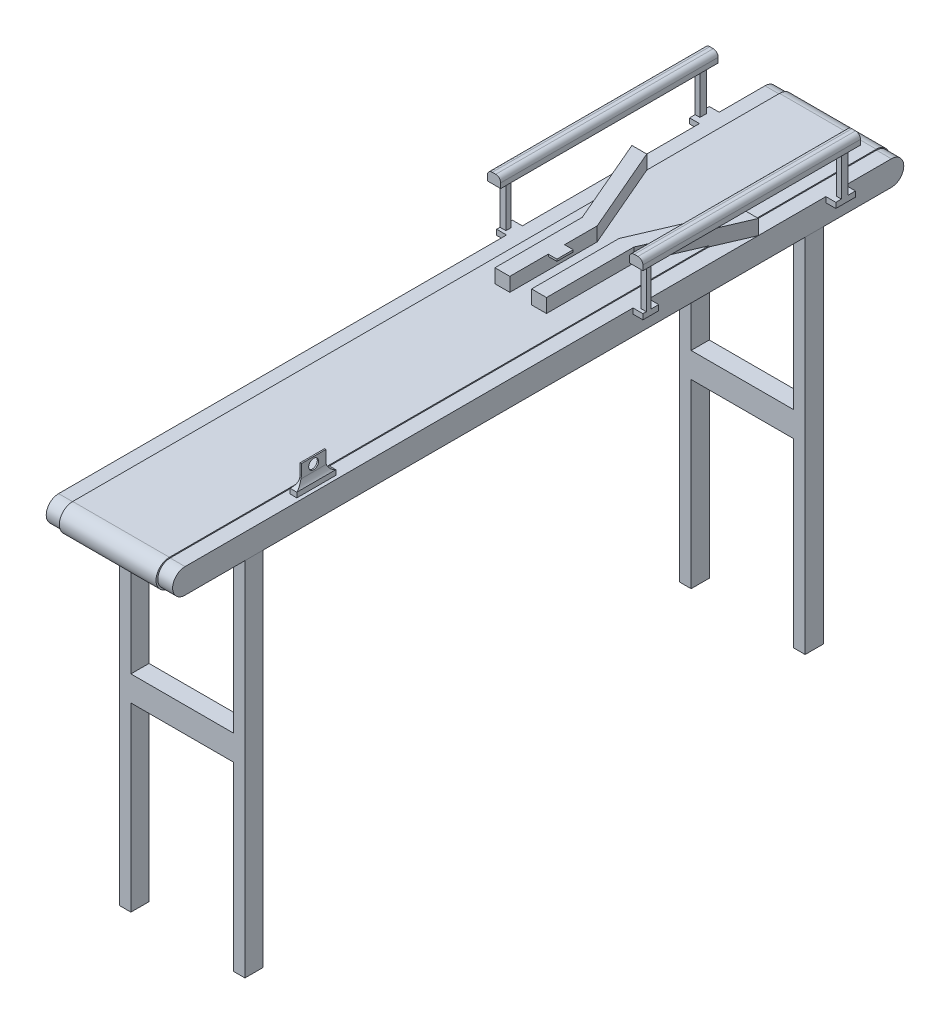
SolidWorks part; units mm, degrees
ref_plane "Alzado" through (0, 0, 0) normal (0, 0, 1) x (1, 0, 0)
ref_plane "Planta" through (0, 0, 0) normal (0, 1, 0) x (1, 0, 0)
ref_plane "Vista lateral" through (0, 0, 0) normal (1, 0, 0) x (0, 0, -1)
sketch "Croquis1" plane through (0, 0, 0) normal (0, 1, 0) x (1, 0, 0)
  line L1 (0, 0) -> (-255, 0)
  line L2 (0, 0) -> (0, 1475)
  line L3 (0, 1475) -> (-255, 1475)
  line L4 (-255, 0) -> (-255, 1475)
  dimension "D1" = 255
  dimension "D2" = 1475
extrude "Saliente-Extruir1" add sketch "Croquis1" along normal blind 50
sketch "Croquis2" plane through (-255, 0, 0) normal (-1, 0, 0) x (0, 0, 1)
  line L0 (6.4584, -12.3806) -> (-25, 0)
  line L4 (-1481.2344, 62.3806) -> (-1449.776, 50)
  line L8 (-1449.776, 0) -> (-1480.215, -12.0359)
  line L9 (-1480.215, -12.0359) -> (-1481.2344, 62.3806)
  line L11 (-25, 50) -> (5.439, 62.0359)
  line L12 (5.439, 62.0359) -> (6.4584, -12.3806)
  line L13 (-1475, 0) -> (0, 0) construction
  arc A4 (-25, 50) -> (-25, 0) centre (-25, 25) cw
  arc A5 (-1449.776, 0) -> (-1449.776, 50) centre (-1449.776, 25) cw
extrude "Cortar-Extruir1" cut sketch "Croquis2" against normal through all
sketch "Croquis5" plane through (-255, 0, 0) normal (-1, 0, 0) x (0, 0, 1)
  line L0 (-1449.776, 0) -> (-25, 0) construction
  line L2 (-1449.276, 52) -> (-23.5, 52)
  line L3 (-23.5, -2) -> (-1449.276, -2)
  arc A1 (-23.5, -2) -> (-23.5, 52) centre (-23.5, 25) ccw
  arc A2 (-25, 0) -> (-25, 50) centre (-25, 25) ccw construction
  arc A3 (-1449.276, 52) -> (-1449.276, -2) centre (-1449.276, 25) ccw
  arc A5 (-1449.776, 50) -> (-1449.776, 0) centre (-1449.776, 25) ccw construction
  point P18 (-1474.776, 25)
  point P19 (-1476.276, 25)
  dimension "D1" = 27
  dimension "D3" = 1.5
  dimension "D5" = 27
  dimension "D2" = 25
  dimension "D4" = 25
  dimension "D6" = 1.5
extrude "Saliente-Extruir2" add sketch "Croquis5" against normal blind 195 from offset 30 offset against normal yes
sketch "Croquis6" plane through (0, 0, 0) normal (0, -1, 0) x (1, 0, 0)
  line L0 (-255, -1449.776) -> (-255, -25) construction
  line L1 (-255, -147.7299) -> (-231.9101, -147.7299)
  line L2 (-255, -147.7299) -> (-255, -184.3095)
  line L3 (-255, -184.3095) -> (-231.9101, -184.3095)
  line L4 (-231.9101, -147.7299) -> (-231.9101, -184.3095)
  line L5 (-25, -147.7299) -> (-25, -184.3095)
  line L6 (-25, -147.7299) -> (-1.9101, -147.7299)
  line L7 (-1.9101, -147.7299) -> (-1.9101, -184.3095)
  line L8 (-25, -184.3095) -> (-1.9101, -184.3095)
  line L9 (-25, -1277.7299) -> (-25, -1314.3095)
  line L10 (-25, -1277.7299) -> (-1.9101, -1277.7299)
  line L11 (-1.9101, -1277.7299) -> (-1.9101, -1314.3095)
  line L12 (-25, -1314.3095) -> (-1.9101, -1314.3095)
  line L13 (-255, -1277.7299) -> (-255, -1314.3095)
  line L14 (-255, -1277.7299) -> (-231.9101, -1277.7299)
  line L15 (-231.9101, -1277.7299) -> (-231.9101, -1314.3095)
  line L16 (-255, -1314.3095) -> (-231.9101, -1314.3095)
  dimension "D1" = 2
  dimension "D2" = 2
extrude "Saliente-Extruir3" add sketch "Croquis6" along normal blind 731
sketch "Croquis7" plane through (-1.9101, 0, 0) normal (1, 0, 0) x (0, 0, -1)
  line L0 (147.7299, -731) -> (147.7299, 0) construction
  line L1 (147.7299, -314.7831) -> (184.3095, -314.7831)
  line L2 (147.7299, -314.7831) -> (147.7299, -365.5)
  line L3 (147.7299, -365.5) -> (184.3095, -365.5)
  line L4 (184.3095, -314.7831) -> (184.3095, -365.5)
  line L5 (184.3095, -731) -> (184.3095, 0) construction
  line L6 (1277.7299, -731) -> (1277.7299, 0) construction
  line L7 (1277.7299, -365.5) -> (1314.3095, -365.5)
  line L8 (1277.7299, -365.5) -> (1277.7299, -314.7831)
  line L9 (1277.7299, -314.7831) -> (1314.3095, -314.7831)
  line L10 (1314.3095, -365.5) -> (1314.3095, -314.7831)
  line L11 (1314.3095, -731) -> (1314.3095, 0) construction
extrude "Saliente-Extruir4" add sketch "Croquis7" against normal through all
sketch "Croquis9" plane through (-255, 0, 0) normal (-1, 0, 0) x (0, 0, 1)
  line L0 (-1449.776, 50) -> (-25, 50) construction
  line L1 (-1357.4324, 50) -> (-1317.6624, 50)
  line L2 (-1357.4324, 50) -> (-1357.4324, 39.2137)
  line L3 (-1357.4324, 39.2137) -> (-1317.6624, 39.2137)
  line L4 (-1317.6624, 50) -> (-1317.6624, 39.2137)
  line L5 (-1449.776, 50) -> (-25, 50) construction
  line L6 (-960.3915, 50) -> (-928.5918, 50)
  line L7 (-960.3915, 50) -> (-960.3915, 39.2137)
  line L8 (-960.3915, 39.2137) -> (-928.5918, 39.2137)
  line L9 (-928.5918, 50) -> (-928.5918, 39.2137)
extrude "Saliente-Extruir5" add sketch "Croquis9" against normal blind 275 and the other way blind 20
sketch "Croquis10" plane through (0, 50, 0) normal (0, 1, 0) x (1, 0, 0)
  line L0 (-275, 1317.6624) -> (-275, 1357.4324) construction
  line L1 (-275, 1342.1015) -> (-265.3595, 1342.1015)
  line L2 (-275, 1342.1015) -> (-275, 1328.9734)
  line L3 (-275, 1328.9734) -> (-265.3595, 1328.9734)
  line L4 (-265.3595, 1342.1015) -> (-265.3595, 1328.9734)
  line L5 (20, 1317.6624) -> (20, 1357.4324) construction
  line L6 (20, 1342.1015) -> (9.6893, 1342.1015)
  line L7 (20, 1342.1015) -> (20, 1328.9734)
  line L8 (20, 1328.9734) -> (9.6893, 1328.9734)
  line L9 (9.6893, 1342.1015) -> (9.6893, 1328.9734)
  line L10 (-275, 928.5918) -> (-275, 960.3915) construction
  line L11 (-275, 945.8609) -> (-263.0957, 945.8609)
  line L12 (-275, 945.8609) -> (-275, 935.4336)
  line L13 (-275, 935.4336) -> (-263.0957, 935.4336)
  line L14 (-263.0957, 945.8609) -> (-263.0957, 935.4336)
  line L15 (20, 928.5918) -> (20, 960.3915) construction
  line L16 (20, 944.4917) -> (9.6893, 944.4917)
  line L17 (20, 944.4917) -> (20, 935.4336)
  line L18 (20, 935.4336) -> (9.6893, 935.4336)
  line L19 (9.6893, 944.4917) -> (9.6893, 935.4336)
extrude "Saliente-Extruir6" add sketch "Croquis10" along normal blind 85
sketch "Croquis11" plane through (0, 135, 0) normal (0, 1, 0) x (1, 0, 0)
  line L1 (-283.985, 1357.4324) -> (-256.9224, 1357.4324)
  line L2 (-283.985, 1357.4324) -> (-283.985, 918.6217)
  line L3 (-283.985, 918.6217) -> (-256.9224, 918.6217)
  line L4 (-256.9224, 1357.4324) -> (-256.9224, 918.6217)
  line L5 (29.9826, 1357.4324) -> (2.5883, 1357.4324)
  line L6 (29.9826, 1357.4324) -> (29.9826, 918.6217)
  line L7 (29.9826, 918.6217) -> (2.5883, 918.6217)
  line L8 (2.5883, 1357.4324) -> (2.5883, 918.6217)
extrude "Saliente-Extruir7" add sketch "Croquis11" along normal blind 20
fillet "Redondeo1" radius 10 4 edges at (-283.985, 155, -1138.027) (-256.9224, 155, -1138.027) (29.9826, 155, -1138.027) (2.5883, 155, -1138.027)
sketch "Croquis12" plane through (0, 50, 0) normal (0, 1, 0) x (1, 0, 0)
  line L0 (-225, 1181.4075) -> (-149.5, 1005.7913)
  line L1 (-225, 23.5) -> (-225, 1449.276) construction
  line L2 (-105.5, 1005.7913) -> (-75.5, 1005.7913)
  line L3 (-105.5, 1005.7913) -> (-30, 1181.4075)
  line L4 (-30, 23.5) -> (-30, 1449.276) construction
  line L5 (-30, 1181.4075) -> (0, 1181.4075)
  line L6 (0, 1181.4075) -> (-75.5, 1005.7913)
  line L7 (-225, 1181.4075) -> (-255, 1181.4075)
  line L8 (-255, 1181.4075) -> (-179.5, 1005.7913)
  line L9 (-179.5, 1005.7913) -> (-149.5, 1005.7913)
  dimension "D1" = 119.5
  dimension "D2" = 119.5
  dimension "D3" = 30
  dimension "D4" = 30
  dimension "D5" = 30
  dimension "D6" = 30
extrude "Saliente-Extruir8" add sketch "Croquis12" along normal blind 30
sketch "Croquis13" plane through (0, 50, 0) normal (0, 1, 0) x (1, 0, 0)
  line L0 (-179.5, 829.5827) -> (-149.5, 829.5827)
  line L2 (-149.5, 1005.7913) -> (-149.5, 829.5827)
  line L4 (-105.5, 1005.7913) -> (-105.5, 829.5827)
  line L6 (-179.5, 1005.7913) -> (-179.5, 829.5827)
  line L8 (-75.5, 1005.7913) -> (-75.5, 829.5827)
  line L9 (-105.5, 829.5827) -> (-75.5, 829.5827)
  line L10 (-105.5, 1005.7913) -> (-75.5, 1005.7913)
  line L11 (-179.5, 1005.7913) -> (-149.5, 1005.7913)
extrude "Saliente-Extruir9" add sketch "Croquis13" along normal blind 30
sketch "Croquis14" plane through (0, 80, 0) normal (0, 1, 0) x (1, 0, 0)
  line L0 (-149.5, 1005.7913) -> (-149.5, 829.5827) construction
  line L1 (-149.5, 940.0062) -> (-132.0595, 940.0062)
  line L2 (-149.5, 940.0062) -> (-149.5, 907.1782)
  line L3 (-149.5, 907.1782) -> (-132.0595, 907.1782)
  line L4 (-132.0595, 940.0062) -> (-132.0595, 907.1782)
extrude "Saliente-Extruir10" add sketch "Croquis14" against normal blind 4
sketch "Croquis15" plane through (-255, 0, 0) normal (-1, 0, 0) x (0, 0, 1)
  line L0 (-147.7299, -731) -> (-147.7299, 0) construction
  line L1 (-235.8987, 13.8968) -> (-147.7299, 13.8968)
  line L2 (-235.8987, 13.8968) -> (-235.8987, -115.0214)
  line L3 (-235.8987, -115.0214) -> (-147.7299, -115.0214)
  line L4 (-147.7299, 13.8968) -> (-147.7299, -115.0214)
extrude "Saliente-Extruir11" add sketch "Croquis15" along normal blind 10
sketch "Croquis16" plane through (-265, 0, 0) normal (-1, 0, 0) x (0, 0, 1)
  line L1 (-197.1399, -72.2874) -> (-186.4887, -72.2874)
  line L2 (-197.1399, -72.2874) -> (-197.1399, -96.8099)
  line L3 (-197.1399, -96.8099) -> (-186.4887, -96.8099)
  line L4 (-186.4887, -72.2874) -> (-186.4887, -96.8099)
  line L5 (-147.7299, 13.8968) -> (-235.8987, 13.8968) construction
  circle A0 centre (-191.8143, -27.701) radius 2.5
  point P6 (-191.8143, -72.2874)
  point P10 (-191.8143, 13.8968)
  dimension "D1" = 5
extrude "Saliente-Extruir12" add sketch "Croquis16" along normal blind 5
sketch "Croquis17" plane through (-265, 0, 0) normal (-1, 0, 0) x (0, 0, 1)
  line L0 (-147.7299, 13.8968) -> (-235.8987, 13.8968) construction
  line L1 (-220.8987, -33.9032) -> (-162.7299, -33.9032)
  line L2 (-220.8987, -33.9032) -> (-220.8987, -47.8568)
  line L3 (-220.8987, -47.8568) -> (-162.7299, -47.8568)
  line L4 (-162.7299, -33.9032) -> (-162.7299, -47.8568)
  line L6 (-235.8987, 13.8968) -> (-235.8987, -115.0214) construction
  line L7 (-147.7299, -115.0214) -> (-147.7299, 13.8968) construction
  point P4 (-159.7848, -54.5493)
  dimension "D1" = 47.8
  dimension "D2" = 15
  dimension "D3" = 15
extrude "Saliente-Extruir13" add sketch "Croquis17" along normal blind 2
sketch "Croquis18" plane through (-267, 0, 0) normal (-1, 0, 0) x (0, 0, 1)
  line L0 (-162.7299, -47.8568) -> (-162.7299, -33.9032) construction
  line L1 (-220.8987, -33.9032) -> (-162.7299, -33.9032)
  line L2 (-220.8987, -33.9032) -> (-220.8987, -35.9032)
  line L3 (-220.8987, -35.9032) -> (-162.7299, -35.9032)
  line L4 (-162.7299, -33.9032) -> (-162.7299, -35.9032)
  dimension "D1" = 2
extrude "Saliente-Extruir14" add sketch "Croquis18" along normal blind 40
sketch "Croquis19" plane through (0, 50, 0) normal (0, 1, 0) x (1, 0, 0)
  line L1 (-20.6801, 336.2926) -> (-7.2167, 336.2926)
  line L2 (-20.6801, 336.2926) -> (-20.6801, 257.7564)
  line L3 (-20.6801, 257.7564) -> (-7.2167, 257.7564)
  line L4 (-7.2167, 336.2926) -> (-7.2167, 257.7564)
extrude "Saliente-Extruir15" add sketch "Croquis19" along normal blind 10
sketch "Croquis20" plane through (0, 60, 0) normal (0, 1, 0) x (1, 0, 0)
  line L0 (-7.2167, 336.2926) -> (-20.6801, 336.2926) construction
  line L1 (-15.2884, 321.7755) -> (-12.6084, 321.7755)
  line L2 (-15.2884, 321.7755) -> (-15.2884, 272.2734)
  line L3 (-15.2884, 272.2734) -> (-12.6084, 272.2734)
  line L4 (-12.6084, 321.7755) -> (-12.6084, 272.2734)
  line L5 (-7.2167, 257.7564) -> (-7.2167, 336.2926) construction
  point P6 (-13.9484, 336.2926)
  point P7 (-13.9484, 321.7755)
  point P10 (-7.2167, 297.0245)
  point P11 (-12.6084, 297.0245)
  dimension "D1" = 2.68
extrude "Saliente-Extruir16" add sketch "Croquis20" along normal blind 40
fillet "Redondeo2" radius 20 4 edges at (-13.9484, 60, -321.7755) (-12.6084, 60, -297.0245) (-13.9484, 60, -272.2734) (-15.2884, 60, -297.0245)
sketch "Croquis21" plane through (-12.6084, 0, 0) normal (1, 0, 0) x (0, 0, -1)
  line L0 (272.2734, 100) -> (321.7755, 100) construction
  circle A0 centre (297.0245, 86.8446) radius 10
  point P2 (296.5667, 86.8446)
  point P5 (297.0245, 100)
  dimension "D1" = 20
extrude "Cortar-Extruir2" cut sketch "Croquis21" against normal blind 40
